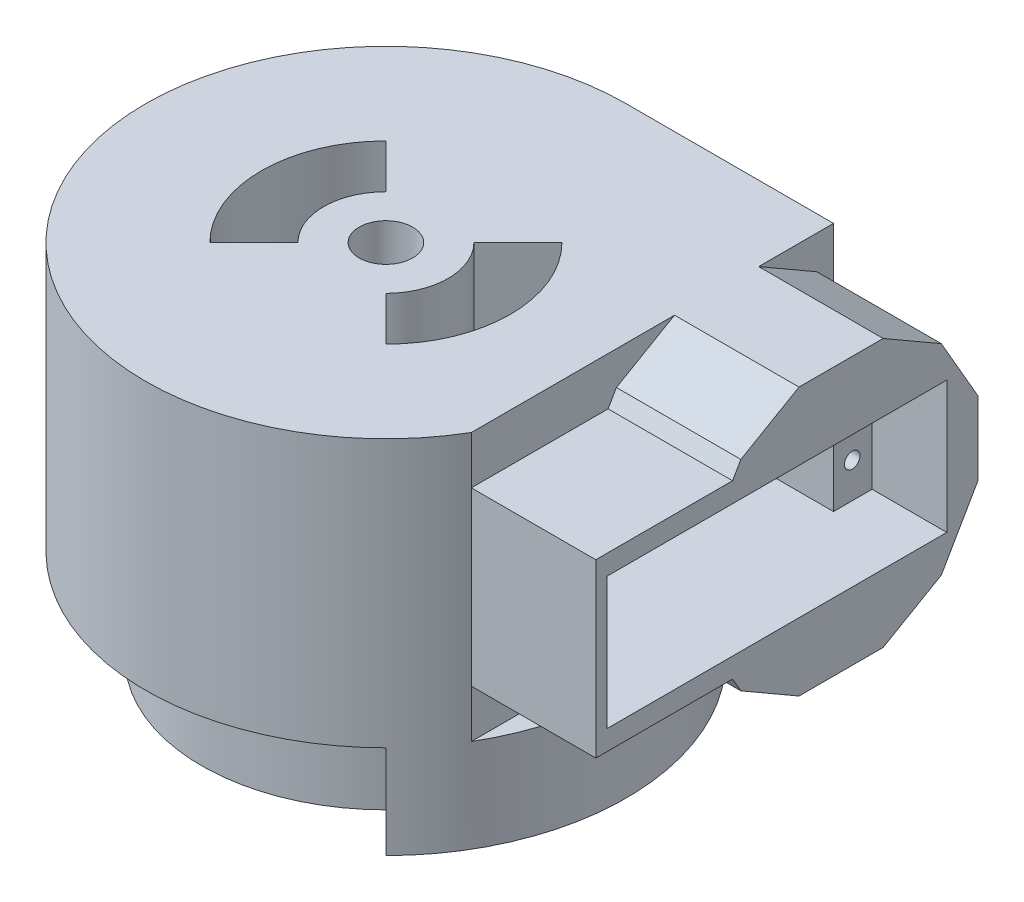
SolidWorks part; units mm, degrees
ref_plane "Front Plane" through (0, 0, 0) normal (0, 0, 1) x (1, 0, 0)
ref_plane "Top Plane" through (0, 0, 0) normal (0, 1, 0) x (1, 0, 0)
ref_plane "Right Plane" through (0, 0, 0) normal (1, 0, 0) x (0, 0, -1)
sketch "Sketch1" plane through (0, 0, 0) normal (0, 1, 0) x (1, 0, 0)
  line L0 (0, 38.625) -> (53.2973, 38.625)
  line L1 (53.2973, 38.625) -> (53.2973, -19.575)
  line L2 (53.2973, -19.575) -> (33.2973, -19.575)
  line L3 (0, 60.3307) -> (0, -56.6529) construction
  arc A0 (0, 38.625) -> (33.2973, -19.575) centre (0, 0) ccw
  dimension "D1" = 20
  dimension "D2" = 38.625
  dimension "D7" = 58.2
extrude "Boss-Extrude1" add sketch "Sketch1" along normal blind 43
sketch "Sketch4" plane through (0, 0, 0) normal (0, -1, 0) x (1, 0, 0)
  line L0 (-38.625, 0) -> (53.2973, 0) construction
  line L1 (53.2973, 19.575) -> (53.2973, -38.625) construction
  line L2 (20.948, 20.948) -> (27.312, 27.312)
  line L3 (20.948, -20.948) -> (27.312, -27.312)
  line L4 (20.948, -20.948) -> (0, 0) construction
  line L5 (0, 0) -> (20.948, 20.948) construction
  arc A0 (33.2973, 19.575) -> (0, -38.625) centre (0, 0) ccw construction
  arc A1 (20.948, 20.948) -> (20.948, -20.948) centre (0, 0) ccw
  arc A4 (27.312, -27.312) -> (27.312, 27.312) centre (0, 0) ccw
  dimension "D1" = 45
  dimension "D2" = 45
  dimension "D3" = 9
extrude "Boss-Extrude2" add sketch "Sketch4" along normal blind 15
sketch "Sketch5" plane through (53.2973, 0, 0) normal (1, 0, 0) x (0, 0, -1)
  line L0 (9.525, 43) -> (9.525, 0) construction
  line L1 (-19.575, 43) -> (38.625, 43) construction
  line L2 (-19.575, 0) -> (38.625, 0) construction
  line L3 (-19.575, 21.5) -> (38.625, 21.5) construction
  line L4 (-19.575, 43) -> (-19.575, 0) construction
  line L5 (38.625, 43) -> (38.625, 0) construction
  line L6 (-14.575, 26.45) -> (-14.575, 16.55) construction
  line L7 (-10.975, 11.5) -> (30.025, 11.5) construction
  line L8 (-10.975, 11.5) -> (-10.975, 31.5) construction
  line L9 (-10.975, 31.5) -> (30.025, 31.5) construction
  line L10 (30.025, 11.5) -> (30.025, 31.5) construction
  line L11 (-10.975, 11.5) -> (30.025, 31.5) construction
  line L12 (-10.975, 31.5) -> (30.025, 11.5) construction
  line L13 (33.625, 26.45) -> (33.625, 16.55) construction
  line L14 (-11.575, 10.9) -> (-11.575, 32.1)
  line L15 (-11.575, 32.1) -> (30.625, 32.1)
  line L16 (30.625, 32.1) -> (30.625, 10.9)
  line L17 (30.625, 10.9) -> (-11.575, 10.9)
  line L18 (-11.575, 10.9) -> (-17.775, 10.9)
  line L19 (-17.775, 10.9) -> (-17.775, 32.1)
  line L20 (-17.775, 32.1) -> (-11.575, 32.1)
  line L21 (30.625, 32.1) -> (36.825, 32.1)
  line L22 (36.825, 32.1) -> (36.825, 10.9)
  line L23 (36.825, 10.9) -> (30.625, 10.9)
  circle A0 centre (-14.575, 26.45) radius 1.25
  circle A1 centre (-14.575, 16.55) radius 1.25
  circle A2 centre (33.625, 16.55) radius 1.25
  circle A3 centre (33.625, 26.45) radius 1.25
  circle A4 centre (19.625, 21.5) radius 6 construction
  point P12 (9.525, 21.5)
  point P25 (-14.575, 21.5)
  point P26 (0, 0)
  point P27 (33.625, 21.5)
  point P38 (9.525, 32.1)
  point P39 (-17.775, 21.5)
  dimension "D8" = 2.5
  dimension "D9" = 2.5
  dimension "D10" = 2.5
  dimension "D11" = 2.5
  dimension "D14" = 12
  dimension "D13" = 17.2
  dimension "D1" = 9.9
  dimension "D2" = 9.9
  dimension "D3" = 24.1
  dimension "D4" = 24.1
  dimension "D5" = 0.6
  dimension "D6" = 20
  dimension "D7" = 54.6
  dimension "D12" = 0.6
  dimension "D15" = 41
extrude "Cut-Extrude1" cut sketch "Sketch5" against normal blind 41 contours L17 L16 L15 L14 region at (53.2973, 21.5, -9.525)
extrude "Cut-Extrude2" cut sketch "Sketch5<5>" against normal blind 12 contours L20 L19 L18 L14 A1 A0 | L23 L22 L21 L16 A3 A2 region at (53.2973, 21.5, 14.6831) region at (53.2973, 21.5, -33.7331)
sketch "Sketch5<5>" plane through (53.2973, 0, 0) normal (1, 0, 0) x (0, 0, -1) same geometry as "Sketch5"
extrude "Cut-Extrude3" cut sketch "Sketch5<6>" against normal blind 35 contours A3 | A2 | A0 | A1 region at (53.2973, 26.45, 14.575) region at (53.2973, 16.55, 14.575) region at (53.2973, 16.55, -33.625) region at (53.2973, 26.45, -33.625)
sketch "Sketch5<6>" plane through (53.2973, 0, 0) normal (1, 0, 0) x (0, 0, -1) same geometry as "Sketch5"
sketch "Sketch6" plane through (0, -15, 0) normal (0, -1, 0) x (1, 0, 0)
  line L0 (0, -38.625) -> (0, 38.625) construction
  line L1 (38.625, 0) -> (-38.625, 0) construction
  line L2 (7.0711, 7.0711) -> (14.1421, 14.1421)
  line L3 (7.0711, -7.0711) -> (14.1421, -14.1421)
  line L4 (0, 0) -> (7.0711, 7.0711) construction
  line L5 (7.0711, -7.0711) -> (0, 0) construction
  line L6 (-7.0711, -7.0711) -> (-14.1421, -14.1421)
  line L7 (-7.0711, 7.0711) -> (-14.1421, 14.1421)
  circle A0 centre (0, 0) radius 4.3
  arc A1 (27.312, 27.312) -> (0, -38.625) centre (0, 0) ccw construction
  arc A2 (27.312, -27.312) -> (27.312, 27.312) centre (0, 0) ccw construction
  arc A3 (7.0711, 7.0711) -> (7.0711, -7.0711) centre (0, 0) cw
  arc A4 (14.1421, -14.1421) -> (14.1421, 14.1421) centre (0, 0) ccw
  arc A5 (-14.1421, -14.1421) -> (-14.1421, 14.1421) centre (0, 0) cw
  arc A6 (-7.0711, 7.0711) -> (-7.0711, -7.0711) centre (0, 0) ccw
  dimension "D1" = 8.6
  dimension "D3" = 10
  dimension "D4" = 10
  dimension "D2" = 45
  dimension "D5" = 45
extrude "Cut-Extrude4" cut sketch "Sketch6" against normal through all both and the other way through all
sketch "Sketch7" plane through (41.2973, 0, 0) normal (1, 0, 0) x (0, 0, -1)
  line L0 (30.625, 32.1) -> (30.625, 10.9) construction
  line L1 (25.625, 18.1) -> (35.625, 18.1)
  line L2 (25.625, 18.1) -> (25.625, 24.9)
  line L3 (25.625, 24.9) -> (35.625, 24.9)
  line L4 (35.625, 18.1) -> (35.625, 24.9)
  line L5 (25.625, 18.1) -> (35.625, 24.9) construction
  line L6 (25.625, 24.9) -> (35.625, 18.1) construction
  point P0 (30.625, 21.5)
  dimension "D1" = 6.8
  dimension "D2" = 10
extrude "Cut-Extrude5" cut sketch "Sketch7" against normal through all from offset 5 offset against normal yes
sketch "Sketch9" plane through (53.2973, 0, 0) normal (1, 0, 0) x (0, 0, -1)
  line L0 (13.9451, 43.5) -> (3.7349, 37.6051)
  line L1 (25.7349, -0.5) -> (35.9451, 5.3949)
  line L2 (35.9451, 5.3949) -> (41.84, 15.6051)
  line L3 (41.84, 15.6051) -> (41.84, 27.3949)
  line L4 (41.84, 27.3949) -> (35.9451, 37.6051)
  line L5 (35.9451, 37.6051) -> (25.7349, 43.5)
  line L6 (25.7349, 43.5) -> (13.9451, 43.5)
  line L7 (3.7349, 37.6051) -> (-2.16, 27.3949)
  line L8 (-2.16, 27.3949) -> (-2.16, 15.6051)
  line L9 (-2.16, 15.6051) -> (3.7349, 5.3949)
  line L10 (3.7349, 5.3949) -> (13.9451, -0.5)
  line L11 (13.9451, -0.5) -> (25.7349, -0.5)
  line L12 (38.625, 43) -> (38.625, 0) construction
  line L13 (-19.575, 43) -> (-19.575, 35.3)
  line L14 (-19.575, 43) -> (-19.575, 0) construction
  line L15 (-19.575, 35.3) -> (2.404, 35.3)
  line L16 (-19.575, 43) -> (13.0791, 43)
  line L17 (26.6009, 43) -> (38.625, 43)
  line L18 (-19.575, 43) -> (38.625, 43) construction
  line L19 (38.625, 43) -> (38.625, 32.9634)
  line L20 (-19.575, 7.7) -> (2.404, 7.7)
  line L21 (-19.575, 7.7) -> (-19.575, 0)
  line L22 (-19.575, 0) -> (13.0791, 0)
  line L23 (-19.575, 0) -> (38.625, 0) construction
  line L24 (-17.775, 32.1) -> (36.825, 32.1) construction
  line L25 (36.825, 10.9) -> (-17.775, 10.9) construction
  line L26 (38.625, 10.0366) -> (38.625, 0)
  line L27 (38.625, 0) -> (26.6009, 0)
  line L28 (38.625, 10.0366) -> (38.625, 32.9634)
  circle A0 centre (19.84, 21.5) radius 22 construction
  line M2 (-19.575, 0) -> (38.625, 0)
  line M3 (38.625, 0) -> (38.625, 43)
  line M4 (38.625, 43) -> (-19.575, 43)
  line M5 (-19.575, 43) -> (-19.575, 0)
  dimension "D1" = 44
  dimension "D2" = 3.2
  dimension "D3" = 3.2
extrude "Cut-Extrude9" cut sketch "Sketch9" against normal up to vertex (20 mm away) contours L5 L4 M3 M4 | L15 L7 L0 M5 M4 | L20 L10 L9 M5 M2 | L2 L1 M2 M3 region at (53.2973, 39.4278, 6.1723) region at (53.2973, 40.2211, -34.8984) region at (53.2973, 3.5722, 6.1723) region at (53.2973, 2.7789, -34.8984) up to point (33.2973, 0, 19.575)
extrude "Boss-Extrude3" add sketch "Sketch9<7>" against normal up to vertex (53.2973 mm away) contours L3 L4 L2 M3 region at (53.2973, 21.5, -40.0606) up to point (0, 43, -38.625)
sketch "Sketch9<7>" plane through (53.2973, 0, 0) normal (1, 0, 0) x (0, 0, -1) same geometry as "Sketch9"
chamfer "Chamfer1" distance 10 angle 45 1 edges at (0, 21.5, -38.625)
